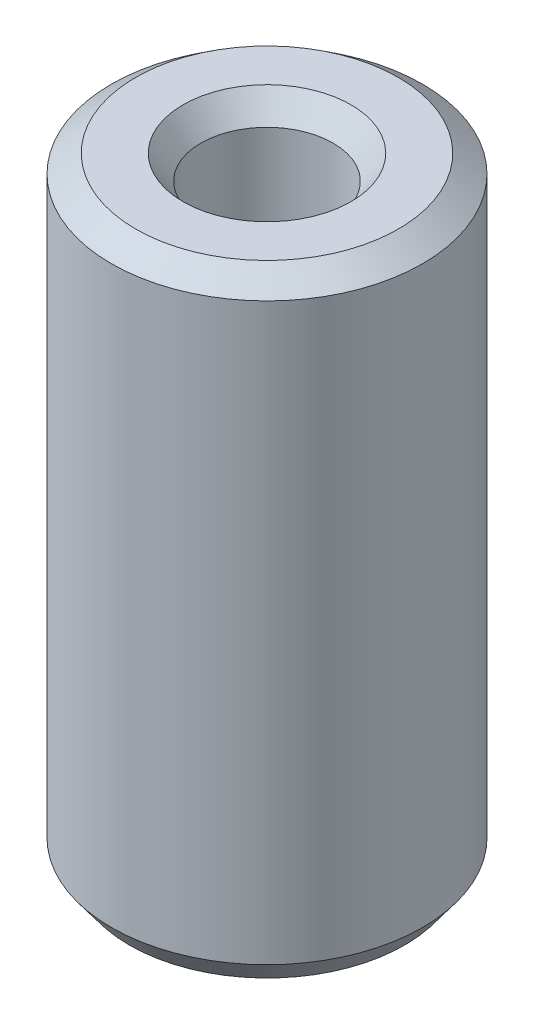
SolidWorks part; units mm, degrees
ref_plane "Front Plane" through (0, 0, 0) normal (0, 0, 1) x (1, 0, 0)
ref_plane "Top Plane" through (0, 0, 0) normal (0, 1, 0) x (1, 0, 0)
ref_plane "Right Plane" through (0, 0, 0) normal (1, 0, 0) x (0, 0, -1)
sketch "Sketch1" plane through (0, 0, 0) normal (0, 1, 0) x (1, 0, 0)
  circle A0 centre (0, 0) radius 7.5
  dimension "SLEEVE_OD" = 15
extrude "Boss-Extrude1" add sketch "Sketch1" along normal blind 29.7445
sketch "Sketch2" plane through (0, 0, 0) normal (0, 1, 0) x (1, 0, 0)
  circle A0 centre (0, 0) radius 3.1844
  dimension "BORE_D" = 6.3689
extrude "Cut-Extrude1" cut sketch "Sketch2" along normal through all
chamfer "Chamfer1" distance 0.8642 angle 53.489 4 edges at (0, 29.7445, 3.1844) (0, 0, 3.1844) (0, 0, 7.5) (0, 29.7445, 7.5) first distance on face at (0, 29.7445, 3.1844) first distance on face at (0, 0, 3.1844) first distance on face at (0, 29.7445, 7.5)
